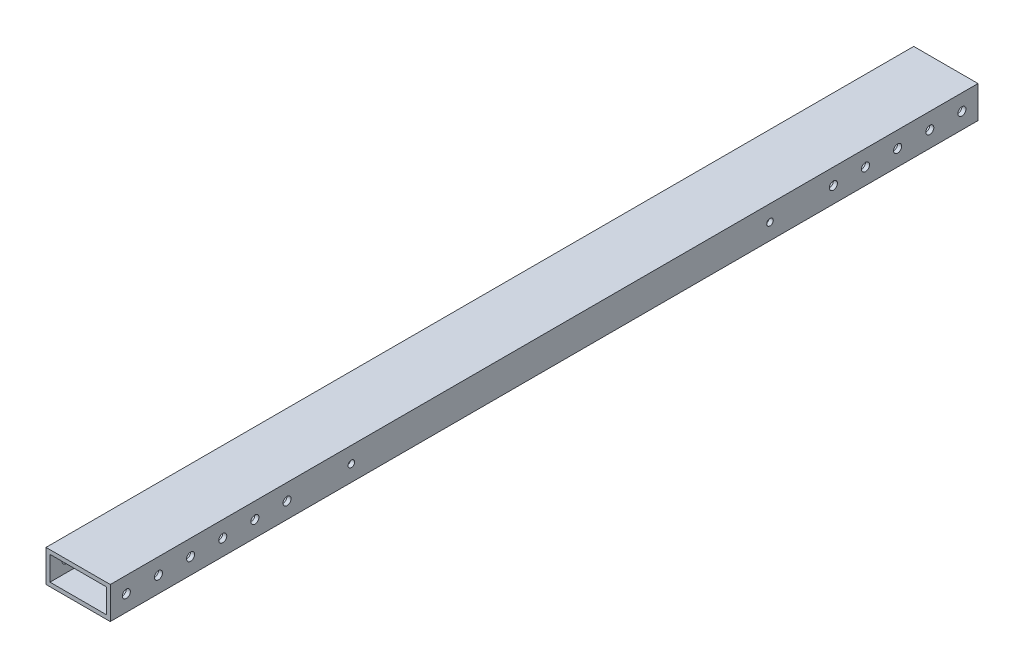
SolidWorks part; units mm, degrees
material "6061 Alloy"
ref_plane "Front Plane" through (0, 0, 0) normal (0, 0, 1) x (1, 0, 0)
ref_plane "Top Plane" through (0, 0, 0) normal (0, 1, 0) x (1, 0, 0)
ref_plane "Right Plane" through (0, 0, 0) normal (1, 0, 0) x (0, 0, -1)
sketch "Sketch1" plane through (0, 0, 0) normal (0, 0, 1) x (1, 0, 0)
  line L0 (-22.225, 9.525) -> (22.225, 9.525)
  line L2 (-25.4, 12.7) -> (25.4, 12.7)
  line L3 (-25.4, 12.7) -> (-25.4, -12.7)
  line L4 (-25.4, -12.7) -> (25.4, -12.7)
  line L5 (25.4, 12.7) -> (25.4, -12.7)
  line L10 (22.225, 9.525) -> (22.225, -9.525)
  line L11 (-22.225, -9.525) -> (22.225, -9.525)
  line L12 (-22.225, 9.525) -> (-22.225, -9.525)
  point P12 (0, 12.7)
  point P14 (25.4, 0)
  dimension "Wall Thickness" = 3.175
  dimension "Outside Width" = 50.8
  dimension "Outside Height" = 25.4
  dimension "Inside Height" = 19.05
  dimension "Inside Width" = 44.45
sketch "Sketch2" plane through (0, 0, 0) normal (1, 0, 0) x (0, 0, -1)
  line L0 (342.9, 0) -> (-342.9, 0)
  point P4 (0, 0)
  point P7 (-342.9, 0)
  point P10 (342.9, 0)
  dimension "Length" = 685.8
sketch "Sketch3" plane through (0, 0, 0) normal (0, 0, 1) x (1, 0, 0)
  line L21 (25.4, 12.7) -> (-25.4, 12.7)
  line L22 (25.4, -12.7) -> (25.4, 12.7)
  line L23 (-25.4, -12.7) -> (25.4, -12.7)
  line L24 (-25.4, 12.7) -> (-25.4, -12.7)
  line L25 (25.4, 12.7) -> (-25.4, 12.7)
  line L26 (25.4, -12.7) -> (25.4, 12.7)
  line L27 (-25.4, -12.7) -> (25.4, -12.7)
  line L28 (-25.4, 12.7) -> (-25.4, -12.7)
  line L29 (22.225, 9.525) -> (-22.225, 9.525)
  line L30 (22.225, -9.525) -> (22.225, 9.525)
  line L31 (-22.225, -9.525) -> (22.225, -9.525)
  line L32 (-22.225, 9.525) -> (-22.225, -9.525)
  line L33 (22.225, 9.525) -> (-22.225, 9.525)
  line L34 (22.225, -9.525) -> (22.225, 9.525)
  line L35 (-22.225, -9.525) -> (22.225, -9.525)
  line L36 (-22.225, 9.525) -> (-22.225, -9.525)
  dimension "D1" = 0
  dimension "D2" = 0
extrude "Boss-Extrude1" add sketch "Sketch3" along normal up to vertex (342.9 mm away) and the other way up to vertex (342.9 mm away) up to point (0, 0, 342.9) other way up to point (0, 0, -342.9)
sketch "Drawing Reference" plane through (0, 0, 0) normal (1, 0, 0) x (0, 0, -1)
  line L0 (-342.9, 0) -> (342.9, 0) construction
  line L1 (0, -12.7) -> (0, 12.7) construction
  line L2 (-342.9, -12.7) -> (342.9, -12.7) construction
  line L5 (-342.9, 12.7) -> (342.9, 12.7) construction
  point P7 (-306.324, 0)
  point P8 (306.324, 0)
  dimension "D1" = 36.576
sketch "Sketch5" plane through (25.4, 0, 0) normal (1, 0, 0) x (0, 0, -1)
  line L0 (-342.9, 0) -> (-279.4, 0)
  line L1 (-342.9, -12.7) -> (-342.9, 12.7) construction
  line L2 (-279.4, 0) -> (-254, 0)
  line L3 (-254, 0) -> (-228.6, 0)
  line L4 (-228.6, 0) -> (-203.2, 0)
sketch "Sketch8" plane through (25.4, 0, 0) normal (1, 0, 0) x (0, 0, -1)
  line L0 (342.9, 0) -> (304.8, 0)
  line L1 (342.9, -12.7) -> (342.9, 12.7) construction
  line L2 (304.8, 0) -> (279.4, 0)
  line L3 (279.4, 0) -> (254, 0)
  line L4 (254, 0) -> (228.6, 0)
  line L5 (342.9, 0) -> (330.2, 0)
hole_wizard "1/4 (0.25) Diameter Hole3" positions "Sketch12" profile "Sketch13" hole size "1/4" standard "ANSI Inch" end condition through all
sketch "Sketch12" plane through (-25.4, 0, 0) normal (-1, 0, 0) x (0, 0, 1)
  point P4 (-330.2, 0)
sketch "Sketch13" plane through (-25.4, 0, -330.2) normal (0, 1, 0) x (0, 0, 1)
  line L0 (0, 0) -> (0, 50.8)
  line L1 (0, 50.8) -> (3.175, 50.8)
  line L2 (3.175, 50.8) -> (3.175, 0)
  line L5 (3.175, 0) -> (0, 0)
  line L11 (0, -6.35) -> (0, 107.95) construction
  dimension "Thru Hole Dia." = 6.35
  dimension "Thru Hole Depth" = 50.8
hole_wizard "1/4 (0.25) Diameter Hole4" positions "Sketch14" profile "Sketch15" hole size "1/4" standard "ANSI Inch" end condition through all
sketch "Sketch14" plane through (-25.4, 0, 0) normal (-1, 0, 0) x (0, 0, 1)
  point P0 (304.8, 0)
  point P3 (330.2, 0)
sketch "Sketch15" plane through (-25.4, 0, 304.8) normal (0, 1, 0) x (0, 0, 1)
  line L0 (0, 0) -> (0, 50.8)
  line L1 (0, 50.8) -> (3.175, 50.8)
  line L2 (3.175, 50.8) -> (3.175, 0)
  line L5 (3.175, 0) -> (0, 0)
  line L11 (0, -6.35) -> (0, 107.95) construction
  dimension "Thru Hole Dia." = 6.35
  dimension "Thru Hole Depth" = 50.8
hole_wizard "1/4 (0.25) Diameter Hole5" positions "Sketch17" profile "Sketch18" hole size "1/4" standard "ANSI Inch" end condition through all
sketch "Sketch17" plane through (25.4, 0, 0) normal (1, 0, 0) x (0, 0, -1)
  point P0 (304.8, 0)
  point P3 (279.4, 0)
sketch "Sketch18" plane through (25.4, 0, -304.8) normal (0, 1, 0) x (0, 0, -1)
  line L0 (0, 0) -> (0, 50.8)
  line L1 (0, 50.8) -> (3.175, 50.8)
  line L2 (3.175, 50.8) -> (3.175, 0)
  line L5 (3.175, 0) -> (0, 0)
  line L11 (0, -6.35) -> (0, 107.95) construction
  dimension "Thru Hole Dia." = 6.35
  dimension "Thru Hole Depth" = 50.8
hole_wizard "1/4 (0.25) Diameter Hole6" positions "Sketch19" profile "Sketch20" hole size "1/4" standard "ANSI Inch" end condition through all
sketch "Sketch19" plane through (25.4, 0, 0) normal (1, 0, 0) x (0, 0, -1)
  point P0 (228.6, 0)
  point P3 (254, 0)
sketch "Sketch20" plane through (25.4, 0, -228.6) normal (0, 1, 0) x (0, 0, -1)
  line L0 (0, 0) -> (0, 50.8)
  line L1 (0, 50.8) -> (3.175, 50.8)
  line L2 (3.175, 50.8) -> (3.175, 0)
  line L5 (3.175, 0) -> (0, 0)
  line L11 (0, -6.35) -> (0, 107.95) construction
  dimension "Thru Hole Dia." = 6.35
  dimension "Thru Hole Depth" = 50.8
hole_wizard "1/4 (0.25) Diameter Hole7" positions "Sketch21" profile "Sketch22" hole size "1/4" standard "ANSI Inch" end condition through all
sketch "Sketch21" plane through (25.4, 0, 0) normal (1, 0, 0) x (0, 0, -1)
  point P0 (-203.2, 0)
  point P3 (-228.6, 0)
sketch "Sketch22" plane through (25.4, 0, 203.2) normal (0, 1, 0) x (0, 0, -1)
  line L0 (0, 0) -> (0, 50.8)
  line L1 (0, 50.8) -> (3.175, 50.8)
  line L2 (3.175, 50.8) -> (3.175, 0)
  line L5 (3.175, 0) -> (0, 0)
  line L11 (0, -6.35) -> (0, 107.95) construction
  dimension "Thru Hole Dia." = 6.35
  dimension "Thru Hole Depth" = 50.8
hole_wizard "1/4 (0.25) Diameter Hole8" positions "Sketch23" profile "Sketch24" hole size "1/4" standard "ANSI Inch" end condition through all
sketch "Sketch23" plane through (25.4, 0, 0) normal (1, 0, 0) x (0, 0, -1)
  point P0 (-279.4, 0)
  point P3 (-254, 0)
sketch "Sketch24" plane through (25.4, 0, 279.4) normal (0, 1, 0) x (0, 0, -1)
  line L0 (0, 0) -> (0, 50.8)
  line L1 (0, 50.8) -> (3.175, 50.8)
  line L2 (3.175, 50.8) -> (3.175, 0)
  line L5 (3.175, 0) -> (0, 0)
  line L11 (0, -6.35) -> (0, 107.95) construction
  dimension "Thru Hole Dia." = 6.35
  dimension "Thru Hole Depth" = 50.8
sketch "Sketch25" plane through (25.4, 0, 0) normal (1, 0, 0) x (0, 0, -1)
  line L0 (-203.2, 0) -> (-152.4, 0)
  line L1 (228.6, 0) -> (178.5118, 0)
hole_wizard "13/64 (0.20313) Diameter Hole1" positions "Sketch26" profile "Sketch27" hole size "13/64" standard "ANSI Inch" end condition through all
sketch "Sketch26" plane through (25.4, 0, 0) normal (1, 0, 0) x (0, 0, -1)
  point P0 (-152.4, 0)
  point P3 (178.5118, 0)
sketch "Sketch27" plane through (25.4, 0, 152.4) normal (0, 1, 0) x (0, 0, -1)
  line L0 (0, 0) -> (0, 50.8)
  line L1 (0, 50.8) -> (2.5798, 50.8)
  line L2 (2.5798, 50.8) -> (2.5798, 0)
  line L5 (2.5798, 0) -> (0, 0)
  line L11 (0, -6.35) -> (0, 107.95) construction
  dimension "Thru Hole Dia." = 5.1595
  dimension "Thru Hole Depth" = 50.8
sketch "Sketch30" plane through (-25.4, 0, 0) normal (-1, 0, 0) x (0, 0, 1)
  point P0 (-128.9434, 0.355)
  point P1 (-103.5434, 0.3445)
  point P2 (77.4316, 0.355)
  point P3 (102.8316, 0.355)
hole_wizard "1/2 (0.5) Diameter Hole1" positions "Sketch33" profile "Sketch34" hole size "1/2" standard "ANSI Inch"
sketch "Sketch33" plane through (-25.4, 0, 0) normal (-1, 0, 0) x (0, 0, 1)
  point P0 (-128.9434, 0.355)
  point P3 (-103.5434, 0.3445)
  point P7 (77.4316, 0.355)
  point P10 (102.8316, 0.355)
sketch "Sketch34" plane through (-25.4, 0.355, -128.9434) normal (0, 1, 0) x (0, 0, 1)
  line L0 (0, 0) -> (0, 10.1655)
  line L1 (0, 10.1655) -> (6.35, 6.35)
  line L2 (6.35, 6.35) -> (6.35, 0)
  line L5 (6.35, 0) -> (0, 0)
  line L10 (0, 10.1655) -> (-6.35, 6.35) construction
  line L11 (0, -6.35) -> (0, 107.95) construction
  dimension "Hole Dia." = 12.7
  dimension "Hole Depth" = 6.35
  dimension "Drill Angle" = 118
equation "\"D1@Drawing Reference\"=\"Outside Width@Sketch1\" * 0.72"
